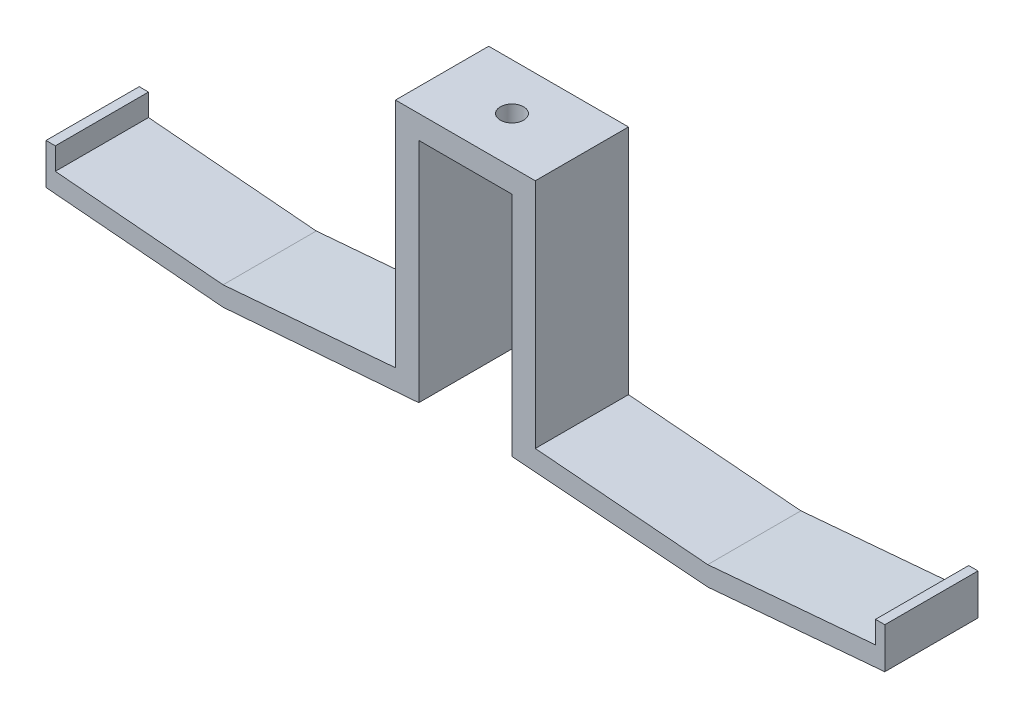
SolidWorks part; units mm, degrees
material "Nylon 6/10"
ref_plane "Front Plane" through (0, 0, 0) normal (0, 0, 1) x (1, 0, 0)
ref_plane "Top Plane" through (0, 0, 0) normal (0, 1, 0) x (1, 0, 0)
ref_plane "Right Plane" through (0, 0, 0) normal (1, 0, 0) x (0, 0, -1)
other "Center of Mass"
sketch "Sketch2" plane through (0, 0, 0) normal (0, 0, 1) x (1, 0, 0)
  line L1 (12.7, 0) -> (12.7, -61.918)
  line L2 (12.7, -61.918) -> (66.04, -66.0514)
  line L3 (66.04, -66.0514) -> (114.3, -61.918)
  line L4 (114.3, -61.918) -> (114.3, -50.8114)
  line L5 (111.76, -50.8114) -> (111.76, -56.838)
  line L6 (111.76, -56.838) -> (66.04, -60.7538)
  line L19 (114.3, -50.8114) -> (111.76, -50.8114)
  line L20 (0, 125.2351) -> (0, -75.9356) construction
  line L21 (12.7, 0) -> (-12.7, 0)
  line L22 (0, 0) -> (0, 6.35)
  line L23 (19.05, 6.35) -> (-19.05, 6.35)
  line L24 (19.05, 6.35) -> (19.05, 0)
  line L25 (19.05, 0) -> (19.05, -56.838)
  line L26 (19.05, -56.838) -> (66.04, -60.7538)
  line L27 (-19.05, 0) -> (-19.05, -56.838)
  line L28 (-19.05, 6.35) -> (-19.05, 0)
  line L29 (-12.7, 0) -> (-12.7, -61.918)
  line L30 (-12.7, -61.918) -> (-66.04, -66.0514)
  line L31 (-66.04, -66.0514) -> (-114.3, -61.918)
  line L32 (-114.3, -61.918) -> (-114.3, -50.8114)
  line L33 (-114.3, -50.8114) -> (-111.76, -50.8114)
  line L34 (-111.76, -50.8114) -> (-111.76, -56.838)
  line L35 (-111.76, -56.838) -> (-66.04, -60.7538)
  line L36 (-19.05, -56.838) -> (-66.04, -60.7538)
  dimension "D1" = 19.05
  dimension "D2" = 12.7
  dimension "D3" = 56.838
  dimension "D4" = 3.9158
  dimension "D5" = 61.918
  dimension "D6" = 2.54
  dimension "D7" = 45.72
  dimension "D8" = 46.99
  dimension "D9" = 15.24
  dimension "D10" = 6.35
extrude "Boss-Extrude1" add sketch "Sketch2" along normal blind 25.4 contours L26 L25 L24 L23 L22 L21 L1 L2 L3 L4 L19 L5 L6 | L27 L36 L35 L34 L33 L32 L31 L30 L29 L21 L22 L23 L28 region at (6.35, 1.353, 0) region at (-6.35, 1.353, 0)
sketch "Sketch3" plane through (0, 6.35, 0) normal (0, 1, 0) x (1, 0, 0)
  line L0 (19.05, -12.7) -> (-19.05, -12.7) construction
  line L1 (19.05, -25.4) -> (19.05, 0) construction
  line L2 (-19.05, -25.4) -> (-19.05, 0) construction
  circle A0 centre (0, -12.7) radius 3.175
  dimension "D1" = 6.35
extrude "Cut-Extrude1" cut sketch "Sketch3" against normal up to next
